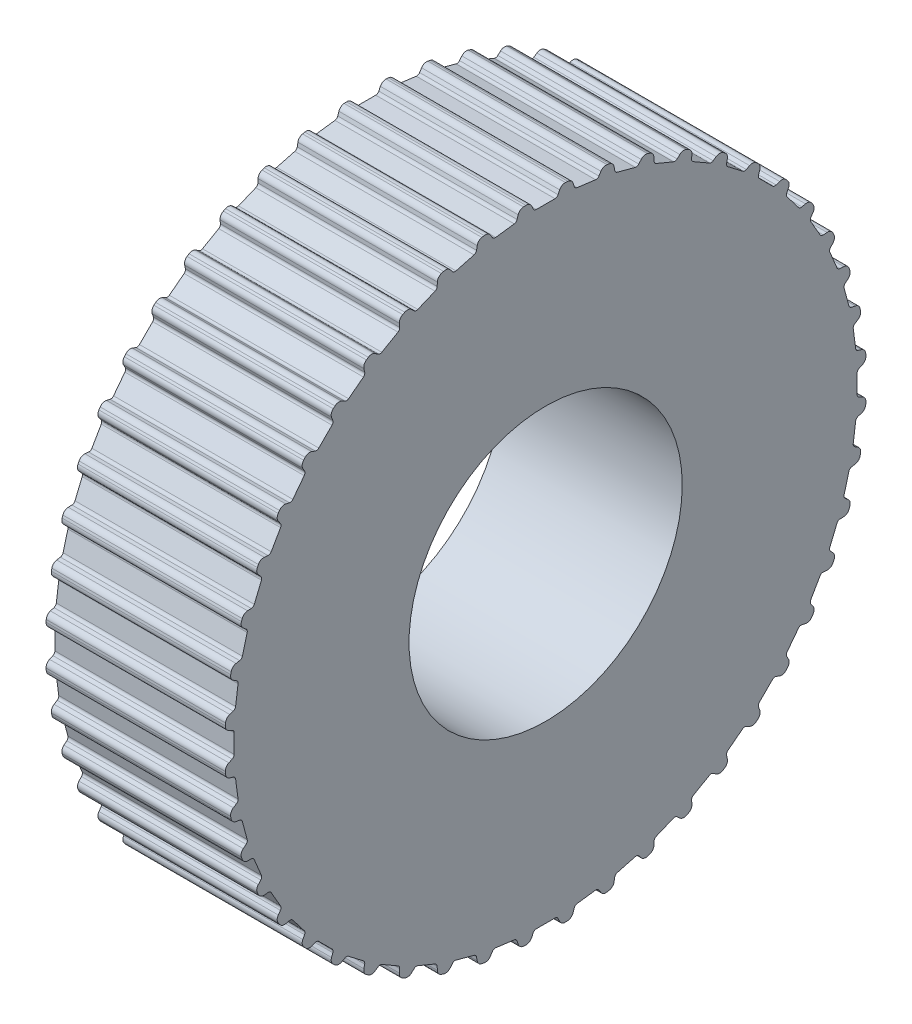
SolidWorks part; units mm, degrees
ref_plane "Front Plane" through (0, 0, 0) normal (0, 0, 1) x (1, 0, 0)
ref_plane "Top Plane" through (0, 0, 0) normal (0, 1, 0) x (1, 0, 0)
ref_plane "Right Plane" through (0, 0, 0) normal (1, 0, 0) x (0, 0, -1)
ref_plane "Plane1" through (0, 0, 0) normal (0, 0, -1) x (-1, 0, 0)
sketch "Sketch1" plane through (0, 0, 0) normal (0, 0, -1) x (-1, 0, 0)
  line L0 (-21, 37.585) -> (-21, 0)
  line L1 (-21, 0) -> (0, 0)
  line L2 (0, 0) -> (0, 37.585)
  line L3 (0, 37.585) -> (-21, 37.585)
  line L4 (-21, 0) -> (0, 0) construction
revolve "Revolve1" add sketch "Sketch1" angle 360 about L4 reverse direction yes
sketch "Sketch2" plane through (0, 0, 0) normal (-1, 0, 0) x (0, 0, 1)
  line L0 (3.0738, 37.4591) -> (3.4238, 36.3491)
  line L1 (3.4238, 36.3491) -> (6.1007, 35.9967)
  line L2 (6.1007, 35.9967) -> (6.7261, 36.9783)
  arc A0 (6.7261, 36.9783) -> (3.0738, 37.4591) centre (0, 0) ccw
extrude "Cut-Extrude1" cut sketch "Sketch2" against normal through all
sketch "Sketch3" plane through (0, 0, 0) normal (-1, 0, 0) x (0, 0, 1)
  line L0 (7.9369, 36.7374) -> (8.139, 35.5912)
  line L1 (8.139, 35.5912) -> (10.747, 34.8924)
  line L2 (10.747, 34.8924) -> (11.4951, 35.784)
  arc A0 (11.4951, 35.784) -> (7.9369, 36.7374) centre (0, 0) ccw
extrude "Cut-Extrude2" cut sketch "Sketch3" against normal through all
sketch "Sketch4" plane through (0, 0, 0) normal (-1, 0, 0) x (0, 0, 1)
  line L0 (12.6642, 35.3871) -> (12.715, 34.2244)
  line L1 (12.715, 34.2244) -> (15.2094, 33.1911)
  line L2 (15.2094, 33.1911) -> (16.0676, 33.9774)
  arc A0 (16.0676, 33.9774) -> (12.6642, 35.3871) centre (0, 0) ccw
extrude "Cut-Extrude3" cut sketch "Sketch4" against normal through all
sketch "Sketch5" plane through (0, 0, 0) normal (-1, 0, 0) x (0, 0, 1)
  line L0 (17.1748, 33.4314) -> (17.0734, 32.2719)
  line L1 (17.0734, 32.2719) -> (19.4116, 30.9219)
  line L2 (19.4116, 30.9219) -> (20.365, 31.5895)
  arc A0 (20.365, 31.5895) -> (17.1748, 33.4314) centre (0, 0) ccw
extrude "Cut-Extrude4" cut sketch "Sketch5" against normal through all
sketch "Sketch6" plane through (0, 0, 0) normal (-1, 0, 0) x (0, 0, 1)
  line L0 (21.3915, 30.9036) -> (21.1396, 29.7673)
  line L1 (21.1396, 29.7673) -> (23.2817, 28.1237)
  line L2 (23.2817, 28.1237) -> (24.3141, 28.6611)
  arc A0 (24.3141, 28.6611) -> (21.3915, 30.9036) centre (0, 0) ccw
extrude "Cut-Extrude5" cut sketch "Sketch6" against normal through all
sketch "Sketch7" plane through (0, 0, 0) normal (-1, 0, 0) x (0, 0, 1)
  line L0 (25.2423, 27.8471) -> (24.8442, 26.7534)
  line L1 (24.8442, 26.7534) -> (26.7534, 24.8442)
  line L2 (26.7534, 24.8442) -> (27.8471, 25.2423)
  arc A0 (27.8471, 25.2423) -> (25.2423, 27.8471) centre (0, 0) ccw
extrude "Cut-Extrude6" cut sketch "Sketch7" against normal through all
sketch "Sketch8" plane through (0, 0, 0) normal (-1, 0, 0) x (0, 0, 1)
  line L0 (28.6611, 24.3141) -> (28.1237, 23.2817)
  line L1 (28.1237, 23.2817) -> (29.7673, 21.1396)
  line L2 (29.7673, 21.1396) -> (30.9036, 21.3915)
  arc A0 (30.9036, 21.3915) -> (28.6611, 24.3141) centre (0, 0) ccw
extrude "Cut-Extrude7" cut sketch "Sketch8" against normal through all
sketch "Sketch9" plane through (0, 0, 0) normal (-1, 0, 0) x (0, 0, 1)
  line L0 (31.5895, 20.365) -> (30.9219, 19.4116)
  line L1 (30.9219, 19.4116) -> (32.2719, 17.0734)
  line L2 (32.2719, 17.0734) -> (33.4314, 17.1748)
  arc A0 (33.4314, 17.1748) -> (31.5895, 20.365) centre (0, 0) ccw
extrude "Cut-Extrude8" cut sketch "Sketch9" against normal through all
sketch "Sketch10" plane through (0, 0, 0) normal (-1, 0, 0) x (0, 0, 1)
  line L0 (33.9774, 16.0676) -> (33.1911, 15.2094)
  line L1 (33.1911, 15.2094) -> (34.2244, 12.715)
  line L2 (34.2244, 12.715) -> (35.3871, 12.6642)
  arc A0 (35.3871, 12.6642) -> (33.9774, 16.0676) centre (0, 0) ccw
extrude "Cut-Extrude9" cut sketch "Sketch10" against normal through all
sketch "Sketch11" plane through (0, 0, 0) normal (-1, 0, 0) x (0, 0, 1)
  line L0 (35.784, 11.4951) -> (34.8924, 10.747)
  line L1 (34.8924, 10.747) -> (35.5912, 8.139)
  line L2 (35.5912, 8.139) -> (36.7374, 7.9369)
  arc A0 (36.7374, 7.9369) -> (35.784, 11.4951) centre (0, 0) ccw
extrude "Cut-Extrude10" cut sketch "Sketch11" against normal through all
sketch "Sketch12" plane through (0, 0, 0) normal (-1, 0, 0) x (0, 0, 1)
  line L0 (36.9783, 6.7261) -> (35.9967, 6.1007)
  line L1 (35.9967, 6.1007) -> (36.3491, 3.4238)
  line L2 (36.3491, 3.4238) -> (37.4591, 3.0738)
  arc A0 (37.4591, 3.0738) -> (36.9783, 6.7261) centre (0, 0) ccw
extrude "Cut-Extrude11" cut sketch "Sketch12" against normal through all
sketch "Sketch13" plane through (0, 0, 0) normal (-1, 0, 0) x (0, 0, 1)
  line L0 (37.5398, 1.8419) -> (36.485, 1.35)
  line L1 (36.485, 1.35) -> (36.485, -1.35)
  line L2 (36.485, -1.35) -> (37.5398, -1.8419)
  arc A0 (37.5398, -1.8419) -> (37.5398, 1.8419) centre (0, 0) ccw
extrude "Cut-Extrude12" cut sketch "Sketch13" against normal through all
sketch "Sketch14" plane through (0, 0, 0) normal (-1, 0, 0) x (0, 0, 1)
  line L0 (37.4591, -3.0738) -> (36.3491, -3.4238)
  line L1 (36.3491, -3.4238) -> (35.9967, -6.1007)
  line L2 (35.9967, -6.1007) -> (36.9783, -6.7261)
  arc A0 (36.9783, -6.7261) -> (37.4591, -3.0738) centre (0, 0) ccw
extrude "Cut-Extrude13" cut sketch "Sketch14" against normal through all
sketch "Sketch15" plane through (0, 0, 0) normal (-1, 0, 0) x (0, 0, 1)
  line L0 (36.7374, -7.9369) -> (35.5912, -8.139)
  line L1 (35.5912, -8.139) -> (34.8924, -10.747)
  line L2 (34.8924, -10.747) -> (35.784, -11.4951)
  arc A0 (35.784, -11.4951) -> (36.7374, -7.9369) centre (0, 0) ccw
extrude "Cut-Extrude14" cut sketch "Sketch15" against normal through all
sketch "Sketch16" plane through (0, 0, 0) normal (-1, 0, 0) x (0, 0, 1)
  line L0 (35.3871, -12.6642) -> (34.2244, -12.715)
  line L1 (34.2244, -12.715) -> (33.1911, -15.2094)
  line L2 (33.1911, -15.2094) -> (33.9774, -16.0676)
  arc A0 (33.9774, -16.0676) -> (35.3871, -12.6642) centre (0, 0) ccw
extrude "Cut-Extrude15" cut sketch "Sketch16" against normal through all
sketch "Sketch17" plane through (0, 0, 0) normal (-1, 0, 0) x (0, 0, 1)
  line L0 (33.4314, -17.1748) -> (32.2719, -17.0734)
  line L1 (32.2719, -17.0734) -> (30.9219, -19.4116)
  line L2 (30.9219, -19.4116) -> (31.5895, -20.365)
  arc A0 (31.5895, -20.365) -> (33.4314, -17.1748) centre (0, 0) ccw
extrude "Cut-Extrude16" cut sketch "Sketch17" against normal through all
sketch "Sketch18" plane through (0, 0, 0) normal (-1, 0, 0) x (0, 0, 1)
  line L0 (30.9036, -21.3915) -> (29.7673, -21.1396)
  line L1 (29.7673, -21.1396) -> (28.1237, -23.2817)
  line L2 (28.1237, -23.2817) -> (28.6611, -24.3141)
  arc A0 (28.6611, -24.3141) -> (30.9036, -21.3915) centre (0, 0) ccw
extrude "Cut-Extrude17" cut sketch "Sketch18" against normal through all
sketch "Sketch19" plane through (0, 0, 0) normal (-1, 0, 0) x (0, 0, 1)
  line L0 (27.8471, -25.2423) -> (26.7534, -24.8442)
  line L1 (26.7534, -24.8442) -> (24.8442, -26.7534)
  line L2 (24.8442, -26.7534) -> (25.2423, -27.8471)
  arc A0 (25.2423, -27.8471) -> (27.8471, -25.2423) centre (0, 0) ccw
extrude "Cut-Extrude18" cut sketch "Sketch19" against normal through all
sketch "Sketch20" plane through (0, 0, 0) normal (-1, 0, 0) x (0, 0, 1)
  line L0 (24.3141, -28.6611) -> (23.2817, -28.1237)
  line L1 (23.2817, -28.1237) -> (21.1396, -29.7673)
  line L2 (21.1396, -29.7673) -> (21.3915, -30.9036)
  arc A0 (21.3915, -30.9036) -> (24.3141, -28.6611) centre (0, 0) ccw
extrude "Cut-Extrude19" cut sketch "Sketch20" against normal through all
sketch "Sketch21" plane through (0, 0, 0) normal (-1, 0, 0) x (0, 0, 1)
  line L0 (20.365, -31.5895) -> (19.4116, -30.9219)
  line L1 (19.4116, -30.9219) -> (17.0734, -32.2719)
  line L2 (17.0734, -32.2719) -> (17.1748, -33.4314)
  arc A0 (17.1748, -33.4314) -> (20.365, -31.5895) centre (0, 0) ccw
extrude "Cut-Extrude20" cut sketch "Sketch21" against normal through all
sketch "Sketch22" plane through (0, 0, 0) normal (-1, 0, 0) x (0, 0, 1)
  line L0 (16.0676, -33.9774) -> (15.2094, -33.1911)
  line L1 (15.2094, -33.1911) -> (12.715, -34.2244)
  line L2 (12.715, -34.2244) -> (12.6642, -35.3871)
  arc A0 (12.6642, -35.3871) -> (16.0676, -33.9774) centre (0, 0) ccw
extrude "Cut-Extrude21" cut sketch "Sketch22" against normal through all
sketch "Sketch23" plane through (0, 0, 0) normal (-1, 0, 0) x (0, 0, 1)
  line L0 (11.4951, -35.784) -> (10.747, -34.8924)
  line L1 (10.747, -34.8924) -> (8.139, -35.5912)
  line L2 (8.139, -35.5912) -> (7.9369, -36.7374)
  arc A0 (7.9369, -36.7374) -> (11.4951, -35.784) centre (0, 0) ccw
extrude "Cut-Extrude22" cut sketch "Sketch23" against normal through all
sketch "Sketch24" plane through (0, 0, 0) normal (-1, 0, 0) x (0, 0, 1)
  line L0 (6.7261, -36.9783) -> (6.1007, -35.9967)
  line L1 (6.1007, -35.9967) -> (3.4238, -36.3491)
  line L2 (3.4238, -36.3491) -> (3.0738, -37.4591)
  arc A0 (3.0738, -37.4591) -> (6.7261, -36.9783) centre (0, 0) ccw
extrude "Cut-Extrude23" cut sketch "Sketch24" against normal through all
sketch "Sketch25" plane through (0, 0, 0) normal (-1, 0, 0) x (0, 0, 1)
  line L0 (1.8419, -37.5398) -> (1.35, -36.485)
  line L1 (1.35, -36.485) -> (-1.35, -36.485)
  line L2 (-1.35, -36.485) -> (-1.8419, -37.5398)
  arc A0 (-1.8419, -37.5398) -> (1.8419, -37.5398) centre (0, 0) ccw
extrude "Cut-Extrude24" cut sketch "Sketch25" against normal through all
sketch "Sketch26" plane through (0, 0, 0) normal (-1, 0, 0) x (0, 0, 1)
  line L0 (-3.0738, -37.4591) -> (-3.4238, -36.3491)
  line L1 (-3.4238, -36.3491) -> (-6.1007, -35.9967)
  line L2 (-6.1007, -35.9967) -> (-6.7261, -36.9783)
  arc A0 (-6.7261, -36.9783) -> (-3.0738, -37.4591) centre (0, 0) ccw
extrude "Cut-Extrude25" cut sketch "Sketch26" against normal through all
sketch "Sketch27" plane through (0, 0, 0) normal (-1, 0, 0) x (0, 0, 1)
  line L0 (-7.9369, -36.7374) -> (-8.139, -35.5912)
  line L1 (-8.139, -35.5912) -> (-10.747, -34.8924)
  line L2 (-10.747, -34.8924) -> (-11.4951, -35.784)
  arc A0 (-11.4951, -35.784) -> (-7.9369, -36.7374) centre (0, 0) ccw
extrude "Cut-Extrude26" cut sketch "Sketch27" against normal through all
sketch "Sketch28" plane through (0, 0, 0) normal (-1, 0, 0) x (0, 0, 1)
  line L0 (-12.6642, -35.3871) -> (-12.715, -34.2244)
  line L1 (-12.715, -34.2244) -> (-15.2094, -33.1911)
  line L2 (-15.2094, -33.1911) -> (-16.0676, -33.9774)
  arc A0 (-16.0676, -33.9774) -> (-12.6642, -35.3871) centre (0, 0) ccw
extrude "Cut-Extrude27" cut sketch "Sketch28" against normal through all
sketch "Sketch29" plane through (0, 0, 0) normal (-1, 0, 0) x (0, 0, 1)
  line L0 (-17.1748, -33.4314) -> (-17.0734, -32.2719)
  line L1 (-17.0734, -32.2719) -> (-19.4116, -30.9219)
  line L2 (-19.4116, -30.9219) -> (-20.365, -31.5895)
  arc A0 (-20.365, -31.5895) -> (-17.1748, -33.4314) centre (0, 0) ccw
extrude "Cut-Extrude28" cut sketch "Sketch29" against normal through all
sketch "Sketch30" plane through (0, 0, 0) normal (-1, 0, 0) x (0, 0, 1)
  line L0 (-21.3915, -30.9036) -> (-21.1396, -29.7673)
  line L1 (-21.1396, -29.7673) -> (-23.2817, -28.1237)
  line L2 (-23.2817, -28.1237) -> (-24.3141, -28.6611)
  arc A0 (-24.3141, -28.6611) -> (-21.3915, -30.9036) centre (0, 0) ccw
extrude "Cut-Extrude29" cut sketch "Sketch30" against normal through all
sketch "Sketch31" plane through (0, 0, 0) normal (-1, 0, 0) x (0, 0, 1)
  line L0 (-25.2423, -27.8471) -> (-24.8442, -26.7534)
  line L1 (-24.8442, -26.7534) -> (-26.7534, -24.8442)
  line L2 (-26.7534, -24.8442) -> (-27.8471, -25.2423)
  arc A0 (-27.8471, -25.2423) -> (-25.2423, -27.8471) centre (0, 0) ccw
extrude "Cut-Extrude30" cut sketch "Sketch31" against normal through all
sketch "Sketch32" plane through (0, 0, 0) normal (-1, 0, 0) x (0, 0, 1)
  line L0 (-28.6611, -24.3141) -> (-28.1237, -23.2817)
  line L1 (-28.1237, -23.2817) -> (-29.7673, -21.1396)
  line L2 (-29.7673, -21.1396) -> (-30.9036, -21.3915)
  arc A0 (-30.9036, -21.3915) -> (-28.6611, -24.3141) centre (0, 0) ccw
extrude "Cut-Extrude31" cut sketch "Sketch32" against normal through all
sketch "Sketch33" plane through (0, 0, 0) normal (-1, 0, 0) x (0, 0, 1)
  line L0 (-31.5895, -20.365) -> (-30.9219, -19.4116)
  line L1 (-30.9219, -19.4116) -> (-32.2719, -17.0734)
  line L2 (-32.2719, -17.0734) -> (-33.4314, -17.1748)
  arc A0 (-33.4314, -17.1748) -> (-31.5895, -20.365) centre (0, 0) ccw
extrude "Cut-Extrude32" cut sketch "Sketch33" against normal through all
sketch "Sketch34" plane through (0, 0, 0) normal (-1, 0, 0) x (0, 0, 1)
  line L0 (-33.9774, -16.0676) -> (-33.1911, -15.2094)
  line L1 (-33.1911, -15.2094) -> (-34.2244, -12.715)
  line L2 (-34.2244, -12.715) -> (-35.3871, -12.6642)
  arc A0 (-35.3871, -12.6642) -> (-33.9774, -16.0676) centre (0, 0) ccw
extrude "Cut-Extrude33" cut sketch "Sketch34" against normal through all
sketch "Sketch35" plane through (0, 0, 0) normal (-1, 0, 0) x (0, 0, 1)
  line L0 (-35.784, -11.4951) -> (-34.8924, -10.747)
  line L1 (-34.8924, -10.747) -> (-35.5912, -8.139)
  line L2 (-35.5912, -8.139) -> (-36.7374, -7.9369)
  arc A0 (-36.7374, -7.9369) -> (-35.784, -11.4951) centre (0, 0) ccw
extrude "Cut-Extrude34" cut sketch "Sketch35" against normal through all
sketch "Sketch36" plane through (0, 0, 0) normal (-1, 0, 0) x (0, 0, 1)
  line L0 (-36.9783, -6.7261) -> (-35.9967, -6.1007)
  line L1 (-35.9967, -6.1007) -> (-36.3491, -3.4238)
  line L2 (-36.3491, -3.4238) -> (-37.4591, -3.0738)
  arc A0 (-37.4591, -3.0738) -> (-36.9783, -6.7261) centre (0, 0) ccw
extrude "Cut-Extrude35" cut sketch "Sketch36" against normal through all
sketch "Sketch37" plane through (0, 0, 0) normal (-1, 0, 0) x (0, 0, 1)
  line L0 (-37.5398, -1.8419) -> (-36.485, -1.35)
  line L1 (-36.485, -1.35) -> (-36.485, 1.35)
  line L2 (-36.485, 1.35) -> (-37.5398, 1.8419)
  arc A0 (-37.5398, 1.8419) -> (-37.5398, -1.8419) centre (0, 0) ccw
extrude "Cut-Extrude36" cut sketch "Sketch37" against normal through all
sketch "Sketch38" plane through (0, 0, 0) normal (-1, 0, 0) x (0, 0, 1)
  line L0 (-37.4591, 3.0738) -> (-36.3491, 3.4238)
  line L1 (-36.3491, 3.4238) -> (-35.9967, 6.1007)
  line L2 (-35.9967, 6.1007) -> (-36.9783, 6.7261)
  arc A0 (-36.9783, 6.7261) -> (-37.4591, 3.0738) centre (0, 0) ccw
extrude "Cut-Extrude37" cut sketch "Sketch38" against normal through all
sketch "Sketch39" plane through (0, 0, 0) normal (-1, 0, 0) x (0, 0, 1)
  line L0 (-36.7374, 7.9369) -> (-35.5912, 8.139)
  line L1 (-35.5912, 8.139) -> (-34.8924, 10.747)
  line L2 (-34.8924, 10.747) -> (-35.784, 11.4951)
  arc A0 (-35.784, 11.4951) -> (-36.7374, 7.9369) centre (0, 0) ccw
extrude "Cut-Extrude38" cut sketch "Sketch39" against normal through all
sketch "Sketch40" plane through (0, 0, 0) normal (-1, 0, 0) x (0, 0, 1)
  line L0 (-35.3871, 12.6642) -> (-34.2244, 12.715)
  line L1 (-34.2244, 12.715) -> (-33.1911, 15.2094)
  line L2 (-33.1911, 15.2094) -> (-33.9774, 16.0676)
  arc A0 (-33.9774, 16.0676) -> (-35.3871, 12.6642) centre (0, 0) ccw
extrude "Cut-Extrude39" cut sketch "Sketch40" against normal through all
sketch "Sketch41" plane through (0, 0, 0) normal (-1, 0, 0) x (0, 0, 1)
  line L0 (-33.4314, 17.1748) -> (-32.2719, 17.0734)
  line L1 (-32.2719, 17.0734) -> (-30.9219, 19.4116)
  line L2 (-30.9219, 19.4116) -> (-31.5895, 20.365)
  arc A0 (-31.5895, 20.365) -> (-33.4314, 17.1748) centre (0, 0) ccw
extrude "Cut-Extrude40" cut sketch "Sketch41" against normal through all
sketch "Sketch42" plane through (0, 0, 0) normal (-1, 0, 0) x (0, 0, 1)
  line L0 (-30.9036, 21.3915) -> (-29.7673, 21.1396)
  line L1 (-29.7673, 21.1396) -> (-28.1237, 23.2817)
  line L2 (-28.1237, 23.2817) -> (-28.6611, 24.3141)
  arc A0 (-28.6611, 24.3141) -> (-30.9036, 21.3915) centre (0, 0) ccw
extrude "Cut-Extrude41" cut sketch "Sketch42" against normal through all
sketch "Sketch43" plane through (0, 0, 0) normal (-1, 0, 0) x (0, 0, 1)
  line L0 (-27.8471, 25.2423) -> (-26.7534, 24.8442)
  line L1 (-26.7534, 24.8442) -> (-24.8442, 26.7534)
  line L2 (-24.8442, 26.7534) -> (-25.2423, 27.8471)
  arc A0 (-25.2423, 27.8471) -> (-27.8471, 25.2423) centre (0, 0) ccw
extrude "Cut-Extrude42" cut sketch "Sketch43" against normal through all
sketch "Sketch44" plane through (0, 0, 0) normal (-1, 0, 0) x (0, 0, 1)
  line L0 (-24.3141, 28.6611) -> (-23.2817, 28.1237)
  line L1 (-23.2817, 28.1237) -> (-21.1396, 29.7673)
  line L2 (-21.1396, 29.7673) -> (-21.3915, 30.9036)
  arc A0 (-21.3915, 30.9036) -> (-24.3141, 28.6611) centre (0, 0) ccw
extrude "Cut-Extrude43" cut sketch "Sketch44" against normal through all
sketch "Sketch45" plane through (0, 0, 0) normal (-1, 0, 0) x (0, 0, 1)
  line L0 (-20.365, 31.5895) -> (-19.4116, 30.9219)
  line L1 (-19.4116, 30.9219) -> (-17.0734, 32.2719)
  line L2 (-17.0734, 32.2719) -> (-17.1748, 33.4314)
  arc A0 (-17.1748, 33.4314) -> (-20.365, 31.5895) centre (0, 0) ccw
extrude "Cut-Extrude44" cut sketch "Sketch45" against normal through all
sketch "Sketch46" plane through (0, 0, 0) normal (-1, 0, 0) x (0, 0, 1)
  line L0 (-16.0676, 33.9774) -> (-15.2094, 33.1911)
  line L1 (-15.2094, 33.1911) -> (-12.715, 34.2244)
  line L2 (-12.715, 34.2244) -> (-12.6642, 35.3871)
  arc A0 (-12.6642, 35.3871) -> (-16.0676, 33.9774) centre (0, 0) ccw
extrude "Cut-Extrude45" cut sketch "Sketch46" against normal through all
sketch "Sketch47" plane through (0, 0, 0) normal (-1, 0, 0) x (0, 0, 1)
  line L0 (-11.4951, 35.784) -> (-10.747, 34.8924)
  line L1 (-10.747, 34.8924) -> (-8.139, 35.5912)
  line L2 (-8.139, 35.5912) -> (-7.9369, 36.7374)
  arc A0 (-7.9369, 36.7374) -> (-11.4951, 35.784) centre (0, 0) ccw
extrude "Cut-Extrude46" cut sketch "Sketch47" against normal through all
sketch "Sketch48" plane through (0, 0, 0) normal (-1, 0, 0) x (0, 0, 1)
  line L0 (-6.7261, 36.9783) -> (-6.1007, 35.9967)
  line L1 (-6.1007, 35.9967) -> (-3.4238, 36.3491)
  line L2 (-3.4238, 36.3491) -> (-3.0738, 37.4591)
  arc A0 (-3.0738, 37.4591) -> (-6.7261, 36.9783) centre (0, 0) ccw
extrude "Cut-Extrude47" cut sketch "Sketch48" against normal through all
sketch "Sketch49" plane through (0, 0, 0) normal (-1, 0, 0) x (0, 0, 1)
  line L0 (-1.8419, 37.5398) -> (-1.35, 36.485)
  line L1 (-1.35, 36.485) -> (1.35, 36.485)
  line L2 (1.35, 36.485) -> (1.8419, 37.5398)
  arc A0 (1.8419, 37.5398) -> (-1.8419, 37.5398) centre (0, 0) ccw
extrude "Cut-Extrude48" cut sketch "Sketch49" against normal through all
sketch "Sketch50" plane through (0, 0, 0) normal (0, 0, -1) x (-1, 0, 0)
  line L0 (-27, 25) -> (-27, 0)
  line L1 (-27, 0) -> (-21, 0)
  line L2 (-21, 0) -> (-21, 25)
  line L3 (-21, 25) -> (-27, 25)
  line L4 (-27, 0) -> (-21, 0) construction
revolve "Revolve2" add sketch "Sketch50" angle 360 about L4 reverse direction yes
hole_wizard "Ø8.0 (8) Diameter Hole1" positions "Sketch52" profile "Sketch51" hole size "Ø8.0" standard "ANSI Metric"
sketch "Sketch52" plane through (27, 0, 0) normal (1, 0, 0) x (0, 0, -1)
  point P0 (0, 0)
sketch "Sketch51" plane through (27, 0, 0) normal (0, 1, 0) x (0, 0, -1)
  line L0 (0, 0) -> (0, 27)
  line L1 (0, 27) -> (4, 27)
  line L2 (4, 27) -> (4, 0)
  line L5 (4, 0) -> (0, 0)
  line L11 (0, -6.35) -> (0, 107.95) construction
  dimension "Thru Hole Dia." = 8
  dimension "Thru Hole Depth" = 27
fillet "Fillet1" radius 0.4 96 edges at (10.5, -19.4116, -30.9219) (10.5, 36.485, -1.35) (10.5, 17.0734, -32.2719) (10.5, 36.3491, 3.4238) (10.5, -32.2719, -17.0734) (10.5, 34.8924, 10.747) (10.5, -1.35, -36.485) (10.5, 35.5912, 8.139) (10.5, 30.9219, -19.4116) (10.5, 33.1911, 15.2094) (10.5, -35.5912, -8.139) (10.5, 34.2244, 12.715) (10.5, -26.7534, -24.8442) (10.5, 30.9219, 19.4116) (10.5, -10.747, -34.8924) (10.5, 32.2719, 17.0734) (10.5, 8.139, -35.5912) (10.5, 28.1237, 23.2817) (10.5, 24.8442, -26.7534) (10.5, 29.7673, 21.1396) (10.5, 34.8924, -10.747) (10.5, 24.8442, 26.7534) (10.5, -36.3491, -3.4238) (10.5, 26.7534, 24.8442) (10.5, -34.2244, -12.715) (10.5, 21.1396, 29.7673) (10.5, -29.7673, -21.1396) (10.5, 23.2817, 28.1237) (10.5, -23.2817, -28.1237) (10.5, 17.0734, 32.2719) (10.5, -15.2094, -33.1911) (10.5, 19.4116, 30.9219) (10.5, -6.1007, -35.9967) (10.5, 12.715, 34.2244) (10.5, 3.4238, -36.3491) (10.5, 15.2094, 33.1911) (10.5, 12.715, -34.2244) (10.5, 8.139, 35.5912) (10.5, 21.1396, -29.7673) (10.5, 10.747, 34.8924) (10.5, 28.1237, -23.2817) (10.5, 3.4238, 36.3491) (10.5, 33.1911, -15.2094) (10.5, 6.1007, 35.9967) (10.5, 35.9967, -6.1007) (10.5, -1.35, 36.485) (10.5, -35.9967, -6.1007) (10.5, 1.35, 36.485) (10.5, -34.8924, -10.747) (10.5, -6.1007, 35.9967) (10.5, -33.1911, -15.2094) (10.5, -3.4238, 36.3491) (10.5, -30.9219, -19.4116) (10.5, -10.747, 34.8924) (10.5, -28.1237, -23.2817) (10.5, -8.139, 35.5912) (10.5, -24.8442, -26.7534) (10.5, -15.2094, 33.1911) (10.5, -21.1396, -29.7673) (10.5, -12.715, 34.2244) (10.5, -17.0734, -32.2719) (10.5, -19.4116, 30.9219) (10.5, -12.715, -34.2244) (10.5, -17.0734, 32.2719) (10.5, -8.139, -35.5912) (10.5, -23.2817, 28.1237) (10.5, -3.4238, -36.3491) (10.5, -21.1396, 29.7673) (10.5, 1.35, -36.485) (10.5, -26.7534, 24.8442) (10.5, 6.1007, -35.9967) (10.5, -24.8442, 26.7534) (10.5, 10.747, -34.8924) (10.5, -29.7673, 21.1396) (10.5, 15.2094, -33.1911) (10.5, -28.1237, 23.2817) (10.5, 19.4116, -30.9219) (10.5, -32.2719, 17.0734) (10.5, 23.2817, -28.1237) (10.5, -30.9219, 19.4116) (10.5, 26.7534, -24.8442) (10.5, -34.2244, 12.715) (10.5, 29.7673, -21.1396) (10.5, -33.1911, 15.2094) (10.5, 32.2719, -17.0734) (10.5, -35.5912, 8.139) (10.5, 34.2244, -12.715) (10.5, -34.8924, 10.747) (10.5, 35.5912, -8.139) (10.5, -36.3491, 3.4238) (10.5, 36.3491, -3.4238) (10.5, -35.9967, 6.1007) (10.5, 36.485, 1.35) (10.5, -36.485, -1.35) (10.5, 35.9967, 6.1007) (10.5, -36.485, 1.35) tangent propagation no
fillet "Fillet2" radius 0.7 96 edges at (10.5, -20.365, -31.5895) (10.5, 36.9783, 6.7261) (10.5, 17.1748, -33.4314) (10.5, 37.4591, 3.0738) (10.5, -33.4314, -17.1748) (10.5, 35.784, 11.4951) (10.5, -1.8419, -37.5398) (10.5, 36.7374, 7.9369) (10.5, 31.5895, -20.365) (10.5, 33.9774, 16.0676) (10.5, -36.7374, -7.9369) (10.5, 35.3871, 12.6642) (10.5, -27.8471, -25.2423) (10.5, 31.5895, 20.365) (10.5, -11.4951, -35.784) (10.5, 33.4314, 17.1748) (10.5, 7.9369, -36.7374) (10.5, 28.6611, 24.3141) (10.5, 25.2423, -27.8471) (10.5, 30.9036, 21.3915) (10.5, 35.784, -11.4951) (10.5, 25.2423, 27.8471) (10.5, -37.4591, -3.0738) (10.5, 27.8471, 25.2423) (10.5, -35.3871, -12.6642) (10.5, 21.3915, 30.9036) (10.5, -30.9036, -21.3915) (10.5, 24.3141, 28.6611) (10.5, -24.3141, -28.6611) (10.5, 17.1748, 33.4314) (10.5, -16.0676, -33.9774) (10.5, 20.365, 31.5895) (10.5, -6.7261, -36.9783) (10.5, 12.6642, 35.3871) (10.5, 3.0738, -37.4591) (10.5, 16.0676, 33.9774) (10.5, 12.6642, -35.3871) (10.5, 7.9369, 36.7374) (10.5, 21.3915, -30.9036) (10.5, 11.4951, 35.784) (10.5, 28.6611, -24.3141) (10.5, 3.0738, 37.4591) (10.5, 33.9774, -16.0676) (10.5, 6.7261, 36.9783) (10.5, 36.9783, -6.7261) (10.5, -1.8419, 37.5398) (10.5, -36.9783, -6.7261) (10.5, 1.8419, 37.5398) (10.5, -35.784, -11.4951) (10.5, -6.7261, 36.9783) (10.5, -33.9774, -16.0676) (10.5, -3.0738, 37.4591) (10.5, -31.5895, -20.365) (10.5, -11.4951, 35.784) (10.5, -28.6611, -24.3141) (10.5, -7.9369, 36.7374) (10.5, -25.2423, -27.8471) (10.5, -16.0676, 33.9774) (10.5, -21.3915, -30.9036) (10.5, -12.6642, 35.3871) (10.5, -17.1748, -33.4314) (10.5, -20.365, 31.5895) (10.5, -12.6642, -35.3871) (10.5, -17.1748, 33.4314) (10.5, -7.9369, -36.7374) (10.5, -24.3141, 28.6611) (10.5, -3.0738, -37.4591) (10.5, -21.3915, 30.9036) (10.5, 1.8419, -37.5398) (10.5, -27.8471, 25.2423) (10.5, 6.7261, -36.9783) (10.5, -25.2423, 27.8471) (10.5, 11.4951, -35.784) (10.5, -30.9036, 21.3915) (10.5, 16.0676, -33.9774) (10.5, -28.6611, 24.3141) (10.5, 20.365, -31.5895) (10.5, -33.4314, 17.1748) (10.5, 24.3141, -28.6611) (10.5, -31.5895, 20.365) (10.5, 27.8471, -25.2423) (10.5, -35.3871, 12.6642) (10.5, 30.9036, -21.3915) (10.5, -33.9774, 16.0676) (10.5, 33.4314, -17.1748) (10.5, -36.7374, 7.9369) (10.5, 35.3871, -12.6642) (10.5, -35.784, 11.4951) (10.5, 36.7374, -7.9369) (10.5, -37.4591, 3.0738) (10.5, 37.4591, -3.0738) (10.5, -36.9783, 6.7261) (10.5, 37.5398, 1.8419) (10.5, -37.5398, -1.8419) (10.5, -37.5398, 1.8419) (10.5, 37.5398, -1.8419) tangent propagation no
sketch "Sketch53" plane through (27, 0, 0) normal (1, 0, 0) x (0, 0, -1)
  circle A0 centre (0, 0) radius 16
  dimension "D1" = 32
extrude "Cut-Extrude49" cut sketch "Sketch53" against normal through all
sketch "Sketch54" plane through (27, 0, 0) normal (1, 0, 0) x (0, 0, -1)
  circle A1 centre (0, 0) radius 25
  circle A2 centre (0, 0) radius 25
  dimension "D1" = 0
extrude "Cut-Extrude50" cut sketch "Sketch54" against normal up to surface (6 mm away) up to face at (21, 0, -25)
